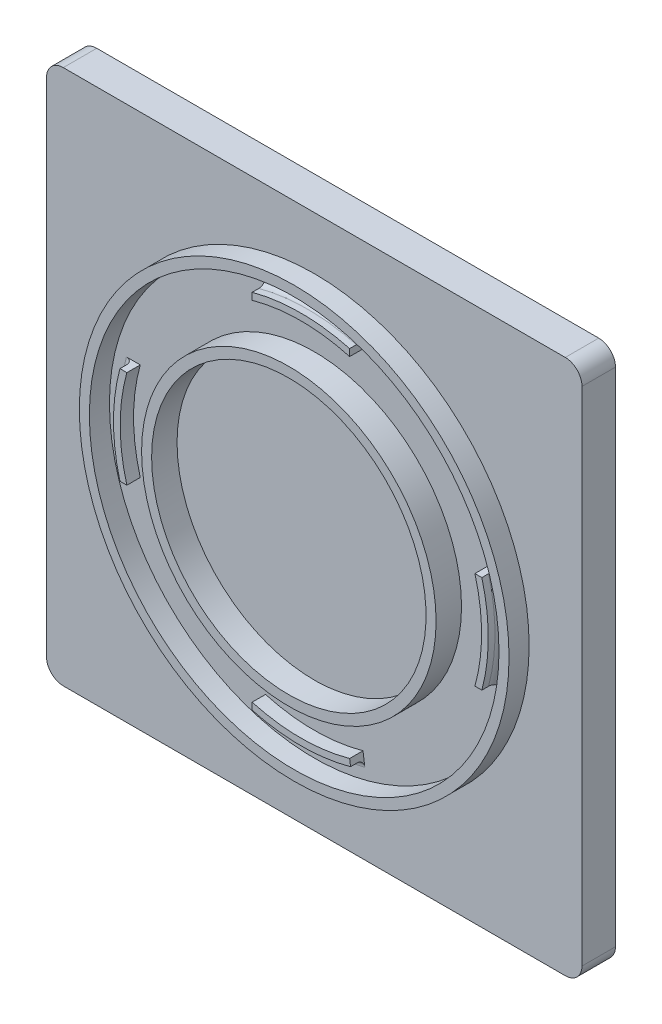
SolidWorks part; units mm, degrees
ref_plane "Front Plane" through (0, 0, 0) normal (0, 0, 1) x (1, 0, 0)
ref_plane "Top Plane" through (0, 0, 0) normal (0, 1, 0) x (1, 0, 0)
ref_plane "Right Plane" through (0, 0, 0) normal (1, 0, 0) x (0, 0, -1)
sketch "Sketch1" plane through (0, 0, 0) normal (0, 0, 1) x (1, 0, 0)
  line L1 (-40, 40) -> (40, 40)
  line L2 (-40, 40) -> (-40, -40)
  line L3 (-40, -40) -> (40, -40)
  line L4 (40, 40) -> (40, -40)
  line L5 (-40, 40) -> (40, -40) construction
  line L6 (-40, -40) -> (40, 40) construction
  point P0 (0, 0)
  dimension "D1" = 80
  dimension "D2" = 80
extrude "Boss-Extrude1" add sketch "Sketch1" along normal blind 5
fillet "Fillet1" radius 2.5 4 edges at (40, 40, 2.5) (-40, 40, 2.5) (40, -40, 2.5) (-40, -40, 2.5)
sketch "Sketch5" plane through (0, 0, 5) normal (0, 0, 1) x (1, 0, 0)
  line L0 (-7.2842, -25.9989) -> (-7.2842, -27.0359)
  line L2 (-7.2842, 27.0359) -> (-7.2842, 25.9989)
  line L4 (7.2842, 27.0359) -> (7.2842, 25.9989)
  line L7 (-27.0359, 7.2842) -> (-25.9989, 7.2842)
  line L9 (-27.0359, -7.2842) -> (-25.9989, -7.2842)
  line L13 (25.9989, -7.2842) -> (27.0359, -7.2842)
  line L14 (25.9989, 7.2842) -> (27.0359, 7.2842)
  line L15 (7.2842, -25.9989) -> (7.4205, -26.9988)
  arc A0 (-27.0359, 7.2842) -> (-27.0359, -7.2842) centre (0, 0) ccw
  arc A1 (-25.9989, 7.2842) -> (-25.9989, -7.2842) centre (0, 0) ccw
  arc A2 (7.2842, 25.9989) -> (-7.2842, 25.9989) centre (0, 0) ccw
  arc A3 (7.2842, 27.0359) -> (-7.2842, 27.0359) centre (0, 0) ccw
  arc A4 (-7.2842, -25.9989) -> (7.2842, -25.9989) centre (0, 0) ccw
  arc A5 (-7.2842, -27.0359) -> (7.4205, -26.9988) centre (0, 0) ccw
  arc A6 (25.9989, -7.2842) -> (25.9989, 7.2842) centre (0, 0) ccw
  arc A7 (27.0359, -7.2842) -> (27.0359, 7.2842) centre (0, 0) ccw
  dimension "D1" = 54
  dimension "D2" = 56
extrude "Boss-Extrude5" add sketch "Sketch5" along normal blind 2
fillet "Fillet2" radius 1 4 edges at (-28, 0, 5) (0, 28, 5) (28, 0, 5) (0.0706, -27.9999, 5)
sketch "Sketch10" plane through (0, 0, 5) normal (0, 0, 1) x (1, 0, 0)
  circle A0 centre (0, 0) radius 22
  circle A1 centre (0, 0) radius 20.5
  dimension "D1" = 44
  dimension "D2" = 41
extrude "Boss-Extrude7" add sketch "Sketch10" along normal blind 3.8
sketch "Sketch12" plane through (0, 0, 5) normal (0, 0, 1) x (1, 0, 0)
  circle A0 centre (0, 0) radius 30.6
  circle A1 centre (0, 0) radius 32.1
  dimension "D1" = 61.2
  dimension "D2" = 64.2
extrude "Boss-Extrude8" add sketch "Sketch12" along normal blind 3
